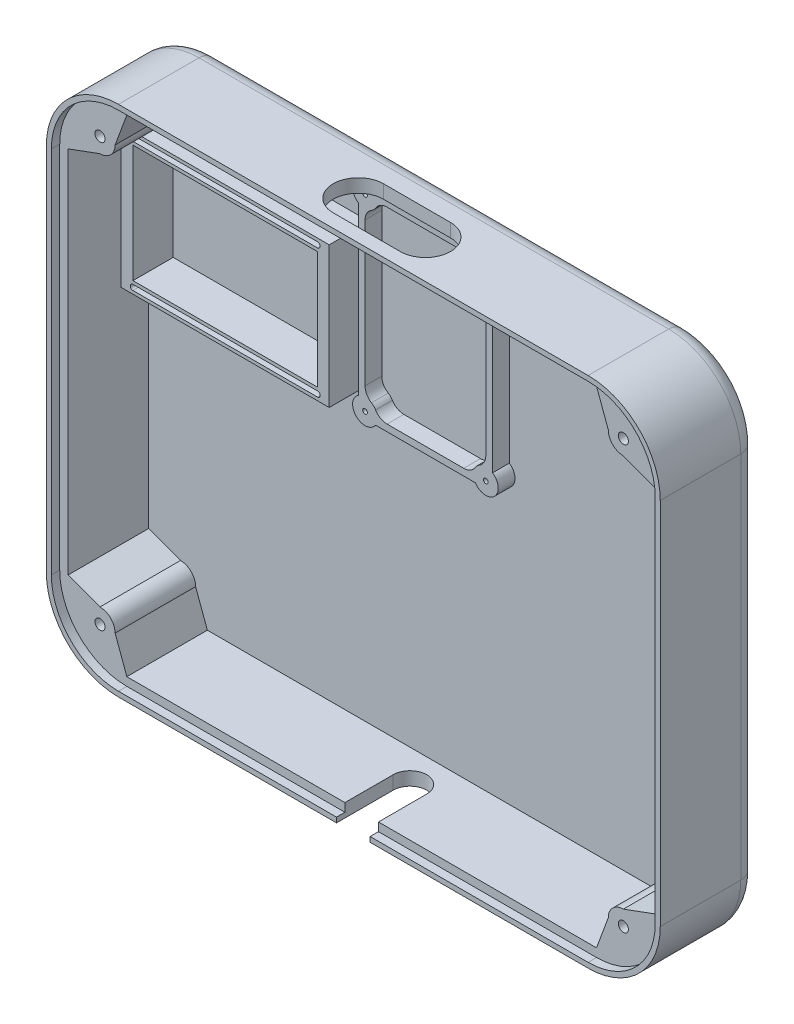
SolidWorks part; units mm, degrees
ref_plane "Front Plane" through (0, 0, 0) normal (0, 0, 1) x (1, 0, 0)
ref_plane "Top Plane" through (0, 0, 0) normal (0, 1, 0) x (1, 0, 0)
ref_plane "Right Plane" through (0, 0, 0) normal (1, 0, 0) x (0, 0, -1)
sketch "Sketch1" plane through (0, 0, 0) normal (0, 0, 1) x (1, 0, 0)
  line L0 (-70, 76.5) -> (70, 76.5)
  line L1 (-70, 75) -> (70, 75)
  line L2 (-90, 55) -> (-90, -55)
  line L3 (-70, -75) -> (70, -75)
  line L4 (90, 55) -> (90, -55)
  line L5 (91.5, 55) -> (91.5, -55)
  line L6 (-70, -76.5) -> (70, -76.5)
  line L7 (-91.5, 55) -> (-91.5, -55)
  line L8 (-70, 72.5) -> (70, 72.5)
  line L9 (87.5, 55) -> (87.5, -55)
  line L10 (-70, -72.5) -> (70, -72.5)
  line L11 (-87.5, 55) -> (-87.5, -55)
  arc A0 (70, -75) -> (90, -55) centre (70, -55) ccw
  arc A1 (-90, -55) -> (-70, -75) centre (-70, -55) ccw
  arc A2 (-70, 75) -> (-90, 55) centre (-70, 55) ccw
  arc A3 (70, 75) -> (90, 55) centre (70, 55) cw
  arc A4 (70, 76.5) -> (91.5, 55) centre (70, 55) cw
  arc A5 (70, -76.5) -> (91.5, -55) centre (70, -55) ccw
  arc A6 (-91.5, -55) -> (-70, -76.5) centre (-70, -55) ccw
  arc A7 (-70, 76.5) -> (-91.5, 55) centre (-70, 55) ccw
  arc A8 (70, 72.5) -> (87.5, 55) centre (70, 55) cw
  arc A9 (70, -72.5) -> (87.5, -55) centre (70, -55) ccw
  arc A10 (-87.5, -55) -> (-70, -72.5) centre (-70, -55) ccw
  arc A11 (-70, 72.5) -> (-87.5, 55) centre (-70, 55) ccw
  point P7 (90, -75)
  point P10 (-90, -75)
  point P15 (90, 75)
  dimension "D5" = 20
  dimension "D1" = 75
  dimension "D2" = 90
  dimension "D3" = 150
  dimension "D4" = 180
  dimension "D6" = 1.5
  dimension "D7" = 2.5
extrude "Boss-Extrude1" add sketch "Sketch1" along normal blind 2.5 contours L8 A11 L11 A10 L10 A9 L9 A8 region at (0, 0, 0)
extrude "Boss-Extrude3" add sketch "Sketch1<4>" along normal blind 26.5 contours L2 A1 L3 A0 L4 A3 L1 A2 | L11 A10 L10 A9 L9 A8 L8 A11
sketch "Sketch1<4>" plane through (0, 0, 0) normal (0, 0, 1) x (1, 0, 0) same geometry as "Sketch1"
extrude "Boss-Extrude5" add sketch "Sketch1<6>" along normal blind 29 contours L0 A7 L7 A6 L6 A5 L5 A4 L1 A3 L4 A0 L3 A1 L2 A2 region at (0, 76.2615, 0)
sketch "Sketch1<6>" plane through (0, 0, 0) normal (0, 0, 1) x (1, 0, 0) same geometry as "Sketch1"
sketch "Sketch2" plane through (0, 0, 2.5) normal (0, 0, 1) x (1, 0, 0)
  line L6 (-70, -75) -> (70, -75) construction
  line L7 (90, 55) -> (90, -55) construction
  line L8 (-87.5, 55) -> (-87.5, -55) construction
  line L10 (-70, -75) -> (70, -75) construction
  line L15 (78, -58.5) -> (78, 58.5)
  line L16 (73.5, -63) -> (-73.5, -63)
  line L17 (-78, -58.5) -> (-78, 58.5)
  line L18 (-73.5, 63) -> (73.5, 63)
  line L19 (78, 58.5) -> (87.5, 55)
  line L20 (73.5, 63) -> (70, 72.5)
  line L21 (78, -58.5) -> (87.5, -55)
  line L22 (73.5, -63) -> (70, -72.5)
  line L23 (-73.5, 63) -> (-70, 72.5)
  line L24 (-78, 58.5) -> (-87.5, 55)
  line L25 (-78, -58.5) -> (-87.5, -55)
  line L26 (-73.5, -63) -> (-70, -72.5)
  circle A0 centre (-78, -63) radius 1.5
  circle A1 centre (-78, 63) radius 1.5
  circle A2 centre (78, 63) radius 1.5
  circle A3 centre (78, -63) radius 1.5
  circle A4 centre (-78, -63) radius 4.5
  circle A5 centre (-78, 63) radius 4.5
  circle A6 centre (78, 63) radius 4.5
  circle A7 centre (78, -63) radius 4.5
  arc M4 (-70, 72.5) -> (-87.5, 55) centre (-70, 55) ccw
  arc M6 (-87.5, -55) -> (-70, -72.5) centre (-70, -55) ccw
  arc M8 (70, -72.5) -> (87.5, -55) centre (70, -55) ccw
  arc M10 (87.5, 55) -> (70, 72.5) centre (70, 55) ccw
  dimension "D9" = 3
  dimension "D10" = 3
  dimension "D11" = 3
  dimension "D12" = 3
  dimension "D1" = 126
  dimension "D2" = 156
  dimension "D3" = 12
  dimension "D4" = 156
  dimension "D5" = 126
  dimension "D6" = 12
  dimension "D7" = 9.5
  dimension "D8" = 12
  dimension "D13" = 3
extrude "Boss-Extrude6" add sketch "Sketch2" along normal blind 24 contours A6 L19 L20 M10 | A6 A2 | A7 A3 | A7 L22 L21 M8 | A5 A1 | A5 L23 L24 M4 | A4 L25 L26 M6 | A4 A0 region at (82.8356, -56.9822, 2.5) region at (81.092, -59.908, 2.5) region at (81.357, 59.643, 2.5) region at (74.908, 59.908, 2.5) region at (-81.092, -66.092, 2.5) region at (-71.9822, -67.8356, 2.5) region at (-81.357, 66.357, 2.5) region at (-74.908, 59.908, 2.5)
fillet "Fillet1" radius 5 8 edges at (-85.2028, -70.2028, 0) (-91.5, 0, 0) (-85.2028, 70.2028, 0) (0, 76.5, 0) (85.2028, 70.2028, 0) (0, -76.5, 0) (85.2028, -70.2028, 0) (91.5, 0, 0)
sketch "Sketch3" plane through (0, -76.5, 0) normal (0, -1, 0) x (1, 0, 0)
  line L0 (0, 12.1138) -> (0, 34.9153) construction
  line L1 (-5, 12.1138) -> (-5, 34.9153)
  line L2 (5, 12.1138) -> (5, 34.9153)
  line L3 (-5, 29) -> (5, 29)
  line L4 (-70, 29) -> (70, 29) construction
  arc A0 (-5, 12.1138) -> (5, 12.1138) centre (0, 12.1138) ccw
  arc A1 (5, 34.9153) -> (-5, 34.9153) centre (0, 34.9153) ccw
  point P3 (0, 23.5146)
  dimension "D1" = 5
extrude "Cut-Extrude1" cut sketch "Sketch3" against normal blind 10 contours L1 A0 L2 region at (0, -76.5, 18.5635)
sketch "Sketch4" plane through (0, 0, 2.5) normal (0, 0, 1) x (1, 0, 0)
  line L5 (-70, 72.5) -> (70, 72.5) construction
  line L6 (14.8871, 10.5) -> (-14.8871, 10.5)
  line L7 (-20, 15.6129) -> (-20, 65.3871)
  line L8 (14.8871, 70.5) -> (-14.8871, 70.5)
  line L9 (20, 15.6129) -> (20, 65.3871)
  line L16 (-87.5, 55) -> (-87.5, -55) construction
  line L17 (87.5, 55) -> (87.5, -55) construction
  line L18 (11.4205, 12.5) -> (-11.4205, 12.5)
  line L25 (11.4205, 68.5) -> (-11.4205, 68.5)
  line L28 (-18, 19.0795) -> (-18, 61.9205)
  line L29 (18, 19.0795) -> (18, 61.9205)
  circle A4 centre (18, 12.5) radius 0.7
  circle A5 centre (-18, 12.5) radius 0.7
  circle A6 centre (-18, 68.5) radius 0.7
  circle A7 centre (18, 68.5) radius 0.7
  arc A8 (14.8871, 10.5) -> (20, 15.6129) centre (18, 12.5) ccw
  arc A9 (-20, 15.6129) -> (-14.8871, 10.5) centre (-18, 12.5) ccw
  arc A10 (-16.0779, 65.3384) -> (-14.8384, 66.5779) centre (-18, 68.5) ccw
  arc A11 (14.8384, 66.5779) -> (16.0779, 65.3384) centre (18, 68.5) ccw
  circle A12 centre (-18, 68.5) radius 3.7 construction
  arc A13 (-14.8871, 70.5) -> (-20, 65.3871) centre (-18, 68.5) ccw
  circle A14 centre (18, 68.5) radius 3.7 construction
  arc A15 (20, 65.3871) -> (14.8871, 70.5) centre (18, 68.5) ccw
  circle A16 centre (-18, 12.5) radius 3.7 construction
  arc A17 (-14.8384, 14.4221) -> (-16.0779, 15.6616) centre (-18, 12.5) ccw
  circle A18 centre (18, 12.5) radius 3.7 construction
  arc A19 (16.0779, 15.6616) -> (14.8384, 14.4221) centre (18, 12.5) ccw
  arc A20 (-18, 61.9205) -> (-16.0779, 65.3384) centre (-14, 61.9205) cw
  arc A21 (18, 61.9205) -> (16.0779, 65.3384) centre (14, 61.9205) ccw
  arc A22 (-18, 19.0795) -> (-16.0779, 15.6616) centre (-14, 19.0795) ccw
  arc A23 (18, 19.0795) -> (16.0779, 15.6616) centre (14, 19.0795) cw
  arc A24 (-11.4205, 68.5) -> (-14.8384, 66.5779) centre (-11.4205, 64.5) ccw
  arc A25 (11.4205, 68.5) -> (14.8384, 66.5779) centre (11.4205, 64.5) cw
  arc A26 (-11.4205, 12.5) -> (-14.8384, 14.4221) centre (-11.4205, 16.5) cw
  arc A27 (11.4205, 12.5) -> (14.8384, 14.4221) centre (11.4205, 16.5) ccw
  point P11 (0, 72.5)
  point P38 (18, 16.2)
  dimension "D1" = 1.4
  dimension "D2" = 1.4
  dimension "D3" = 1.4
  dimension "D4" = 1.4
  dimension "D9" = 4
  dimension "D5" = 2
  dimension "D6" = 56
  dimension "D7" = 36
  dimension "D10" = 67.5
  dimension "D11" = 67.5
  dimension "D8" = 3
extrude "Boss-Extrude8" add sketch "Sketch4" along normal blind 5
sketch "Sketch5" plane through (0, 76.5, 0) normal (0, 1, 0) x (1, 0, 0)
  line L0 (10, -17.5) -> (-10, -17.5) construction
  line L1 (10, -25) -> (-10, -25)
  line L2 (10, -10) -> (-10, -10)
  line L3 (-70, -29) -> (70, -29) construction
  arc A0 (10, -25) -> (10, -10) centre (10, -17.5) ccw
  arc A1 (-10, -10) -> (-10, -25) centre (-10, -17.5) ccw
  point P2 (0, -17.5)
  dimension "D1" = 4
  dimension "D2" = 15
  dimension "D3" = 0
  dimension "D4" = 20
extrude "Cut-Extrude3" cut sketch "Sketch5" against normal up to next
sketch "Sketch6" plane through (0, 0, 2.5) normal (0, 0, 1) x (1, 0, 0)
  line L0 (-83.6781, 57.1463) -> (-21.6781, 57.1463)
  line L1 (-80.1781, 53.6463) -> (-25.1781, 53.6463)
  line L2 (-80.1781, 53.6463) -> (-80.1781, 18.6463)
  line L3 (-80.1781, 18.6463) -> (-25.1781, 18.6463)
  line L4 (-25.1781, 53.6463) -> (-25.1781, 18.6463)
  line L5 (-21.6781, 57.1463) -> (-21.6781, 15.1463)
  line L6 (-83.6781, 15.1463) -> (-21.6781, 15.1463)
  line L7 (-83.6781, 57.1463) -> (-83.6781, 15.1463)
  line L9 (-80.1781, 18.6463) -> (-80.1781, 15.1463)
  line L10 (-25.1781, 53.6463) -> (-25.1781, 57.1463)
  line L11 (-25.1781, 57.1463) -> (-25.1781, 18.6463)
  line L12 (-80.1781, 55.3963) -> (-25.1781, 55.3963) construction
  line L13 (-80.1781, 56.1963) -> (-25.1781, 56.1963)
  line L14 (-80.1781, 54.5963) -> (-25.1781, 54.5963)
  line L15 (-80.1781, 16.8963) -> (-25.1781, 16.8963) construction
  line L16 (-80.1781, 17.6963) -> (-25.1781, 17.6963)
  line L17 (-80.1781, 16.0963) -> (-25.1781, 16.0963)
  arc A0 (-80.1781, 56.1963) -> (-80.1781, 54.5963) centre (-80.1781, 55.3963) ccw
  arc A1 (-25.1781, 54.5963) -> (-25.1781, 56.1963) centre (-25.1781, 55.3963) ccw
  arc A2 (-80.1781, 17.6963) -> (-80.1781, 16.0963) centre (-80.1781, 16.8963) ccw
  arc A3 (-25.1781, 16.0963) -> (-25.1781, 17.6963) centre (-25.1781, 16.8963) ccw
  point P14 (-52.6781, 55.3963)
  point P19 (-52.6781, 16.8963)
  point P26 (0, 0)
  line M25 (-78, 58.5) -> (-87.5, 55)
  dimension "D1" = 35
  dimension "D2" = 55
  dimension "D4" = 1.6
  dimension "D5" = 1.6
  dimension "D3" = 3.5
extrude "Boss-Extrude9" add sketch "Sketch6" along normal blind 12 contours A3 L17 L9 L6 L5 L0 L11 A1 L10 L4 L3 L16 | A2 L9 L2 L1 L10 L14 A0 L13 L11 L0 L7 L6 M25 region at (-25.8982, 56.6713, 2.5) region at (-23.4281, 56.4262, 2.5)
